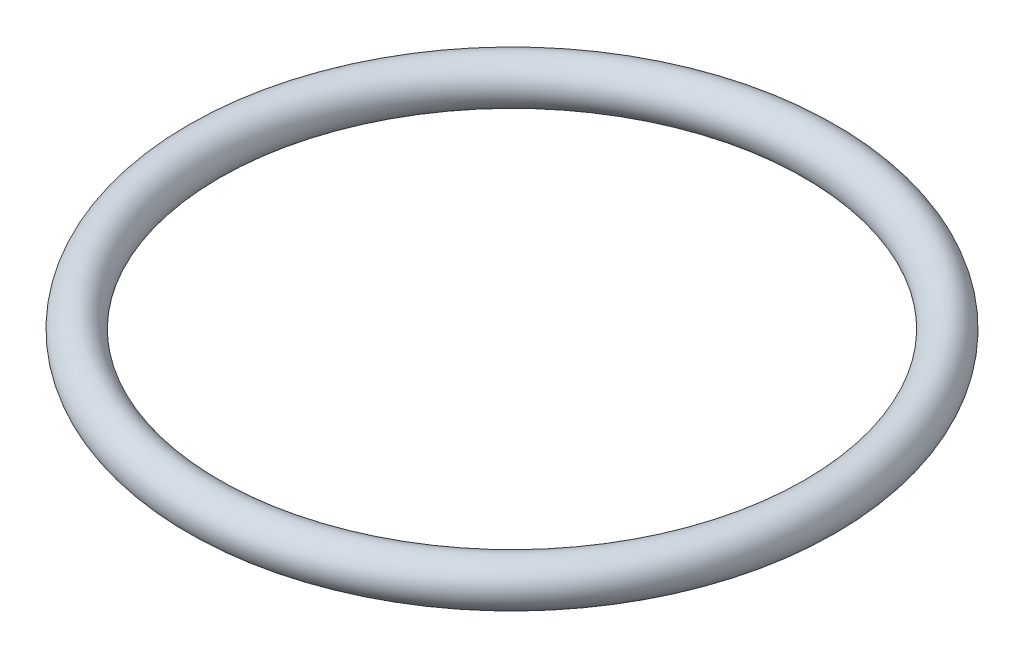
SolidWorks part; units mm, degrees
material "Rubber"
ref_plane "Front Plane" through (0, 0, 0) normal (0, 0, 1) x (1, 0, 0)
ref_plane "Top Plane" through (0, 0, 0) normal (0, 1, 0) x (1, 0, 0)
ref_plane "Right Plane" through (0, 0, 0) normal (1, 0, 0) x (0, 0, -1)
sketch "Sketch1" plane through (0, 0, 0) normal (0, 0, 1) x (1, 0, 0)
  line L0 (55, 0) -> (-55, 0) construction
  line L1 (0, 22.8759) -> (0, -24.4285) construction
  circle A0 centre (-12.8714, 0) radius 0.9081
  dimension "D1" = 1.8161
  dimension "D2" = 23.9268
revolve "Revolve1" add sketch "Sketch1" angle 360 about L1
ref_point "Point1"
ref_axis "Axis1" through (0, 0, 0) along (0, 1, 0)
